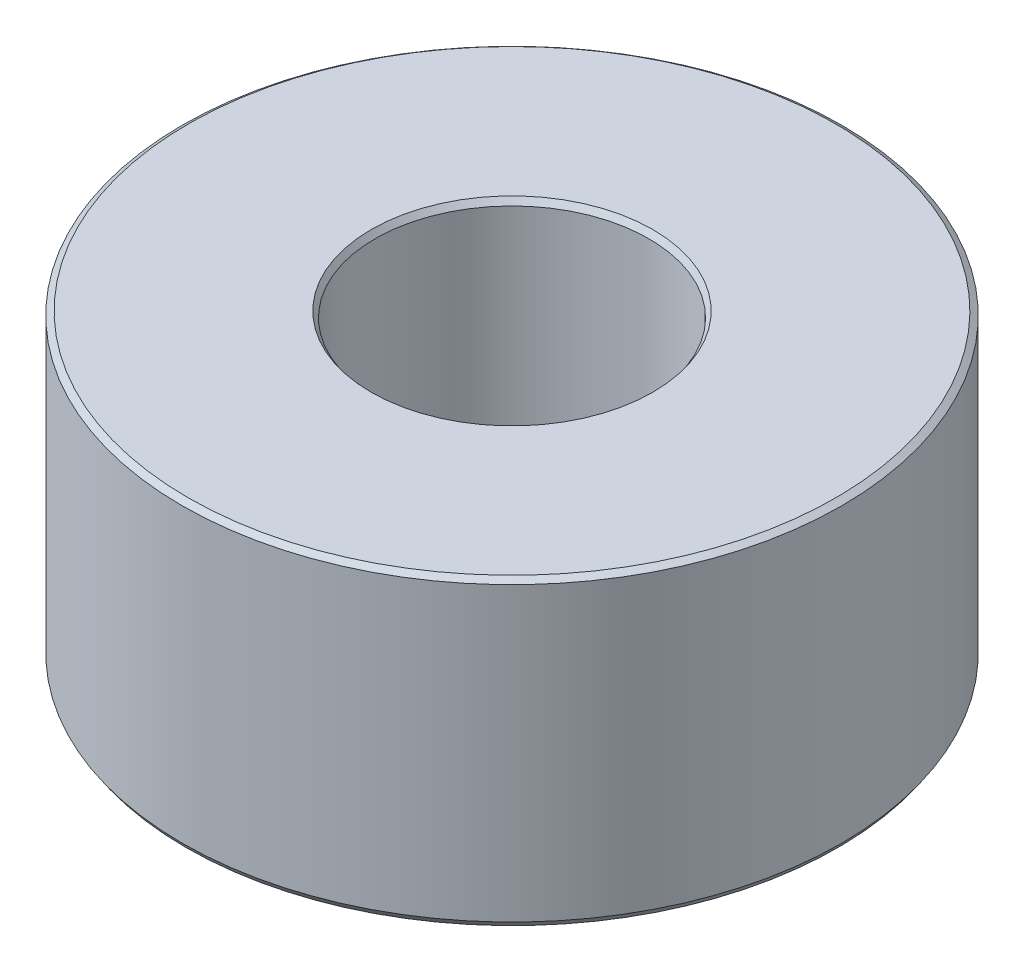
SolidWorks part; units mm, degrees
ref_plane "Front Plane" through (0, 0, 0) normal (0, 0, 1) x (1, 0, 0)
ref_plane "Top Plane" through (0, 0, 0) normal (0, 1, 0) x (1, 0, 0)
ref_plane "Right Plane" through (0, 0, 0) normal (1, 0, 0) x (0, 0, -1)
sketch "Sketch1" plane through (0, 0, 0) normal (0, 1, 0) x (1, 0, 0)
  circle A0 centre (0, 0) radius 60
  dimension "SLEEVE_OD" = 120
extrude "Boss-Extrude1" add sketch "Sketch1" along normal blind 54.9735
sketch "Sketch2" plane through (0, 0, 0) normal (0, 1, 0) x (1, 0, 0)
  circle A0 centre (0, 0) radius 24.912
  dimension "BORE_D" = 49.8241
extrude "Cut-Extrude1" cut sketch "Sketch2" along normal through all
chamfer "Chamfer1" distance 0.7242 angle 56.051 4 edges at (0, 54.9735, 24.912) (0, 0, 24.912) (0, 0, 60) (0, 54.9735, 60) first distance on face at (0, 54.9735, 24.912) first distance on face at (0, 0, 24.912) first distance on face at (0, 54.9735, 60)
